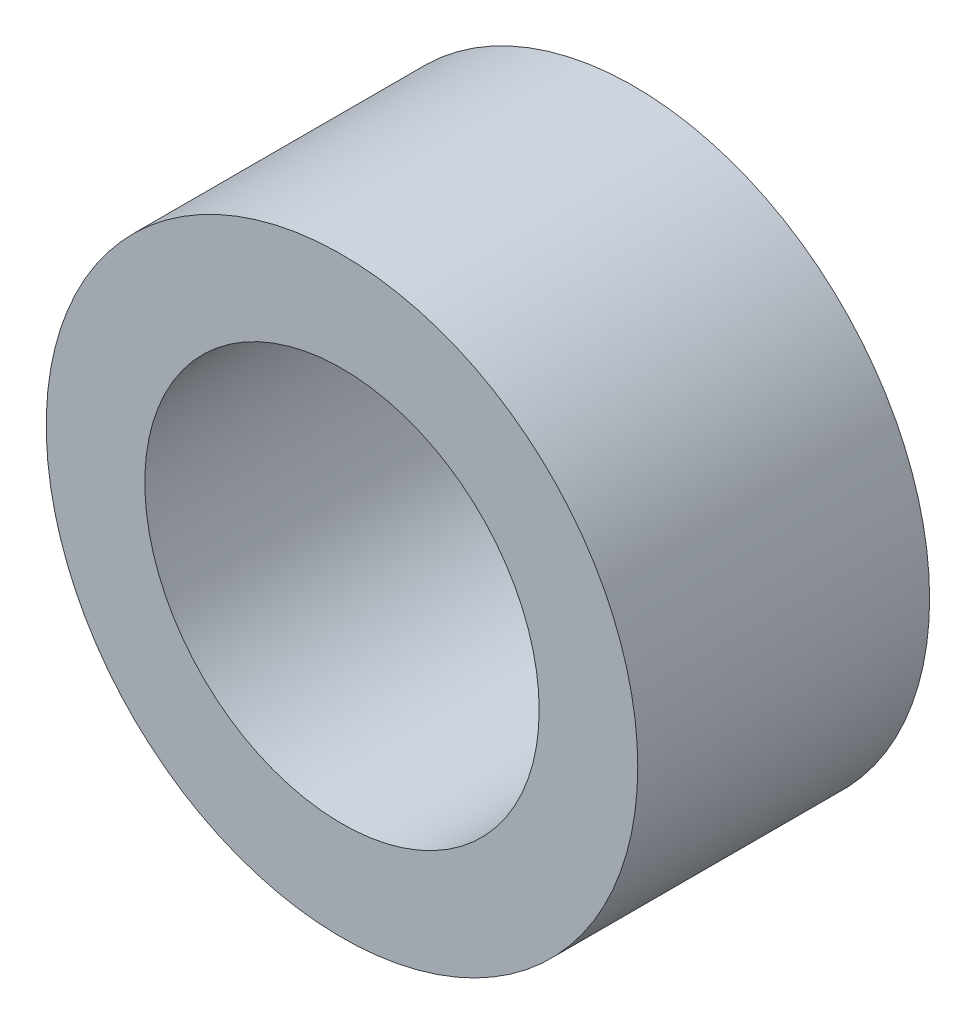
SolidWorks part; units mm, degrees
material "PET"
ref_plane "Front Plane" through (0, 0, 0) normal (0, 0, 1) x (1, 0, 0)
ref_plane "Top Plane" through (0, 0, 0) normal (0, 1, 0) x (1, 0, 0)
ref_plane "Right Plane" through (0, 0, 0) normal (1, 0, 0) x (0, 0, -1)
sketch "Sketch1" plane through (0, 0, 0) normal (0, 0, 1) x (1, 0, 0)
  circle A0 centre (0, 0) radius 6.35
  circle A1 centre (0, 0) radius 9.525
  dimension "D1" = 12.7
  dimension "D2" = 19.05
extrude "Boss-Extrude1" add sketch "Sketch1" along normal mid plane 9.398
